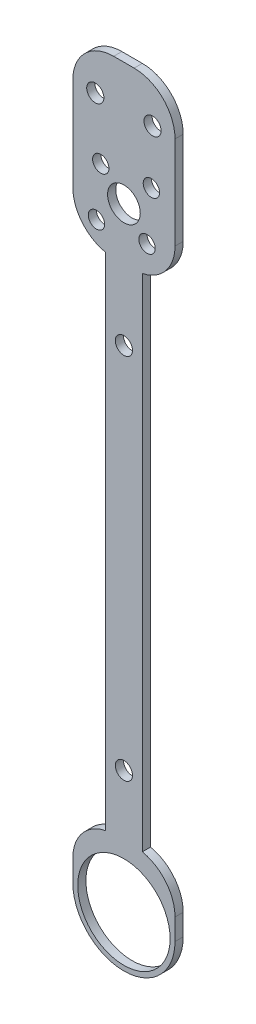
SolidWorks part; units mm, degrees
material "ABS PC"
ref_plane "Front Plane" through (0, 0, 0) normal (0, 0, 1) x (1, 0, 0)
ref_plane "Top Plane" through (0, 0, 0) normal (0, 1, 0) x (1, 0, 0)
ref_plane "Right Plane" through (0, 0, 0) normal (1, 0, 0) x (0, 0, -1)
sketch "Sketch1" plane through (0, 0, 0) normal (0, 0, 1) x (1, 0, 0)
  line L0 (19.2175, 156.7175) -> (5.7825, 143.2825) construction
  line L1 (0, 0) -> (25, 0)
  line L2 (0, 0) -> (0, 150)
  line L3 (0, 150) -> (25, 150)
  line L4 (25, 0) -> (25, 150)
  line L5 (6.8431, 155.6569) -> (18.1569, 144.3431) construction
  line L6 (12.5, 113.5707) -> (12.5, 21.8509) construction
  line L11 (25, 150) -> (0, 150)
  line L12 (25, 150) -> (25, 180)
  line L13 (25, 180) -> (0, 180)
  line L14 (0, 150) -> (0, 180)
  line L15 (25, 137.5) -> (17, 137.5)
  line L16 (25, 137.5) -> (25, 15)
  line L17 (25, 15) -> (17, 15)
  line L18 (17, 137.5) -> (17, 15)
  line L19 (0, 15) -> (8, 15)
  line L20 (8, 137.5) -> (8, 15)
  line L21 (0, 137.5) -> (8, 137.5)
  line L22 (0, 137.5) -> (0, 15)
  circle A1 centre (12.5, 0) radius 12.5
  circle A2 centre (19.2175, 156.7175) radius 2
  circle A3 centre (6.8431, 155.6569) radius 2
  circle A4 centre (5.7825, 143.2825) radius 2
  circle A5 centre (18.1569, 144.3431) radius 2
  circle A6 centre (12.5, 0) radius 11.3
  circle A7 centre (12.5, 150) radius 4
  point P17 (12.5, 150)
  dimension "D4" = 4
  dimension "D5" = 4
  dimension "D6" = 4
  dimension "D7" = 4
  dimension "D10" = 22.6
  dimension "D11" = 8
  dimension "D1" = 25
  dimension "D2" = 150
  dimension "D9" = 45
  dimension "D3" = 16
  dimension "D8" = 19
  dimension "D15" = 25
  dimension "D16" = 30
  dimension "D12" = 8
  dimension "D13" = 122.5
  dimension "D14" = 15
extrude "Boss-Extrude1" add sketch "Sketch1" along normal blind 2 contours A6 L1 A1 | A6 L1 A1 | A7 L3 L2 L21 L20 L19 A1 L4 L17 L18 L15 A5 A4 | A7 L3 L12 L13 L14 A3 A2
fillet "Fillet1" radius 10 6 edges at (25, 15, 1) (0, 15, 1) (25, 137.5, 1) (0, 137.5, 1) (0, 180, 1) (25, 180, 1)
sketch "Sketch2" plane through (0, 0, 0) normal (0, 0, -1) x (-1, 0, 0)
  line L0 (-12.5, 150) -> (-12.5, 0) construction
  circle A0 centre (-12.5, 120) radius 2.1
  circle A1 centre (-12.5, 30) radius 2.1
  circle A2 centre (-19.5, 170) radius 2.1
  circle A3 centre (-5.5, 170) radius 2.1
  dimension "D2" = 4.2
  dimension "D3" = 4.2
  dimension "D6" = 4.2
  dimension "D1" = 12.5
  dimension "D4" = 30
  dimension "D5" = 120
  dimension "D7" = 7
  dimension "D8" = 50
extrude "Cut-Extrude1" cut sketch "Sketch2" against normal through all contours A0 | A1 | A2 | A3
equation "\"diam_bearing\"= 22.6mm"
equation "\"bolt_clearance\"= 4mm"
equation "\"back_clearance\"= 8mm"
equation "\"D10@Sketch1\"=\"diam_bearing\""
equation "\"D11@Sketch1\"=\"back_clearance\""
equation "\"D6@Sketch1\"=\"bolt_clearance\""
equation "\"D5@Sketch1\"=\"bolt_clearance\""
equation "\"D7@Sketch1\"=\"bolt_clearance\""
equation "\"D4@Sketch1\"=\"bolt_clearance\""
equation "\"mid_bolt\"= 4.2mm"
equation "\"D2@Sketch2\"=\"mid_bolt\""
equation "\"D3@Sketch2\"=\"mid_bolt\""
